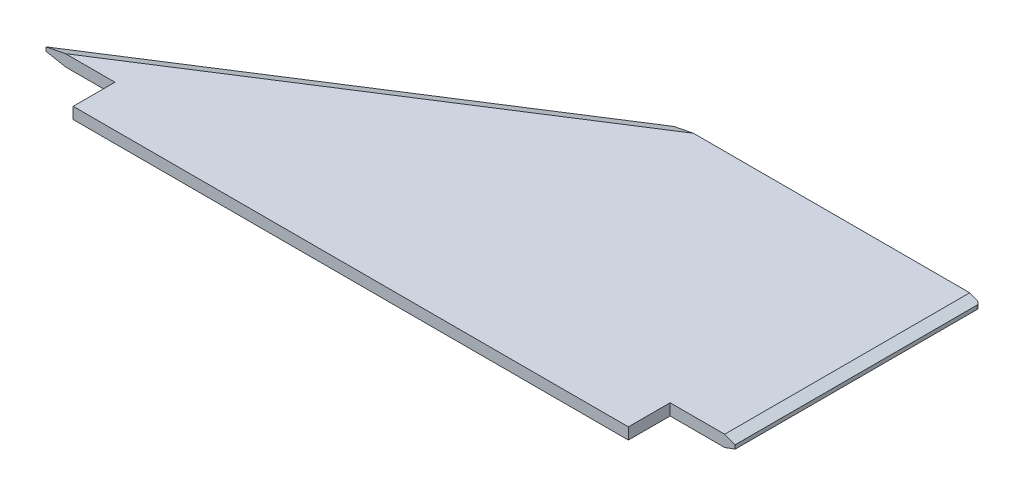
SolidWorks part; units mm, degrees
material "A-Glass Fiber"
ref_plane "Front Plane" through (0, 0, 0) normal (0, 0, 1) x (1, 0, 0)
ref_plane "Top Plane" through (0, 0, 0) normal (0, 1, 0) x (1, 0, 0)
ref_plane "Right Plane" through (0, 0, 0) normal (1, 0, 0) x (0, 0, -1)
sketch "Sketch1" plane through (0, 0, 0) normal (0, 1, 0) x (1, 0, 0)
  line L1 (0, 10.9) -> (100, 74.9)
  line L2 (100, 74.9) -> (180, 74.9)
  line L3 (180, 74.9) -> (180, 10.9)
  line L7 (180, 10.9) -> (163, 10.9)
  line L10 (-989.0676, -29) -> (49010.9324, -29) construction
  line L11 (-1000, 0) -> (0, 0) construction
  line L12 (-999.3384, -58) -> (49000.6616, -58) construction
  line L13 (0, 0) -> (0, -58) construction
  line L15 (163, 0) -> (163, 10.9)
  line L16 (163, 0) -> (49000, 0) construction
  line L17 (0, 10.9) -> (18, 10.9)
  line L18 (18, 10.9) -> (18, 0)
  line L19 (18, 0) -> (163, 0)
  point P6 (0, 0)
  point P15 (0, -29)
  dimension "D1" = 80
  dimension "D2" = 180
  dimension "D3" = 18
  dimension "D4" = 100
  dimension "D5" = 64
  dimension "D6" = 79.8
  dimension "D7" = 58
  dimension "D8" = 145
extrude "Boss-Extrude1" add sketch "Sketch1" along normal blind 3
chamfer "Chamfer1" distance 1 angle 70 2 edges at (180, 3, -42.9) (50, 3, -42.9) first distance on face at (180, 1.5, -42.9) first distance on face at (50, 1.5, -42.9)
chamfer "Chamfer2" distance 1 angle 70 2 edges at (50, 0, -42.9) (180, 0, -42.9) first distance on face at (50, 1, -42.9) first distance on face at (180, 1, -42.9)
fillet "Fillet1" radius 1 1 edges at (180, 1.5, -74.9)
